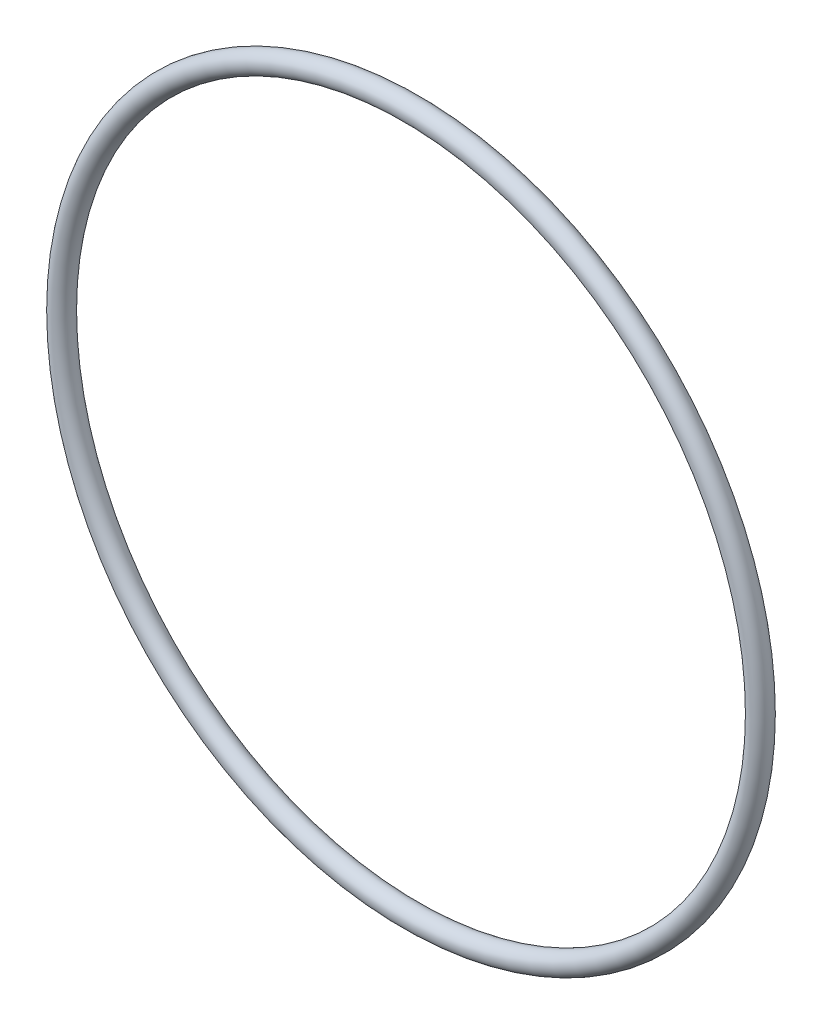
SolidWorks part; units mm, degrees
ref_plane "Front Plane" through (0, 0, 0) normal (0, 0, 1) x (1, 0, 0)
ref_plane "Top Plane" through (0, 0, 0) normal (0, 1, 0) x (1, 0, 0)
ref_plane "Right Plane" through (0, 0, 0) normal (1, 0, 0) x (0, 0, -1)
sketch "Sketch1" plane through (0, 0, 0) normal (0, 0, 1) x (1, 0, 0)
  line L0 (-42.5, 0) -> (42.5, 0) construction
  circle A0 centre (0, 0) radius 42.5
  circle A1 centre (0, 0) radius 40
  point P4 (40, 0)
  point P5 (42.5, 0)
  point P8 (0, 0)
  point P9 (0, 42.5)
  point P10 (0, -42.5)
  dimension "ID" = 80
  dimension "Width" = 2.5
  dimension "OD" = 85
sketch "Sketch2" plane through (0, 0, 0) normal (0, 1, 0) x (1, 0, 0)
  line L0 (-42.5, 0) -> (42.5, 0) construction
  line L1 (0, 1.25) -> (0, -1.25) construction
  circle A0 centre (41.25, 0) radius 1.25
  point P8 (0, 0)
  point P11 (41.25, 1.25)
revolve "Revolve1" add sketch "Sketch2" angle 360 about L1
sketch "Sketch3" plane through (0, 0, 0) normal (1, 0, 0) x (0, 0, -1)
  line L0 (-1.25, 0) -> (1.25, 0) construction
  line L1 (1.25, -41.25) -> (1.25, 41.25) construction
  line L3 (-1.25, 42.5) -> (1.25, 42.5) construction
  line L4 (-1.25, 42.5) -> (-1.25, -42.5) construction
  line L5 (-1.25, -42.5) -> (1.25, -42.5) construction
  line L6 (1.25, 42.5) -> (1.25, -42.5) construction
  point P2 (0, 0)
ref_axis "Axis1" through (0, 0, -1.375) along (0, 0, 1)
